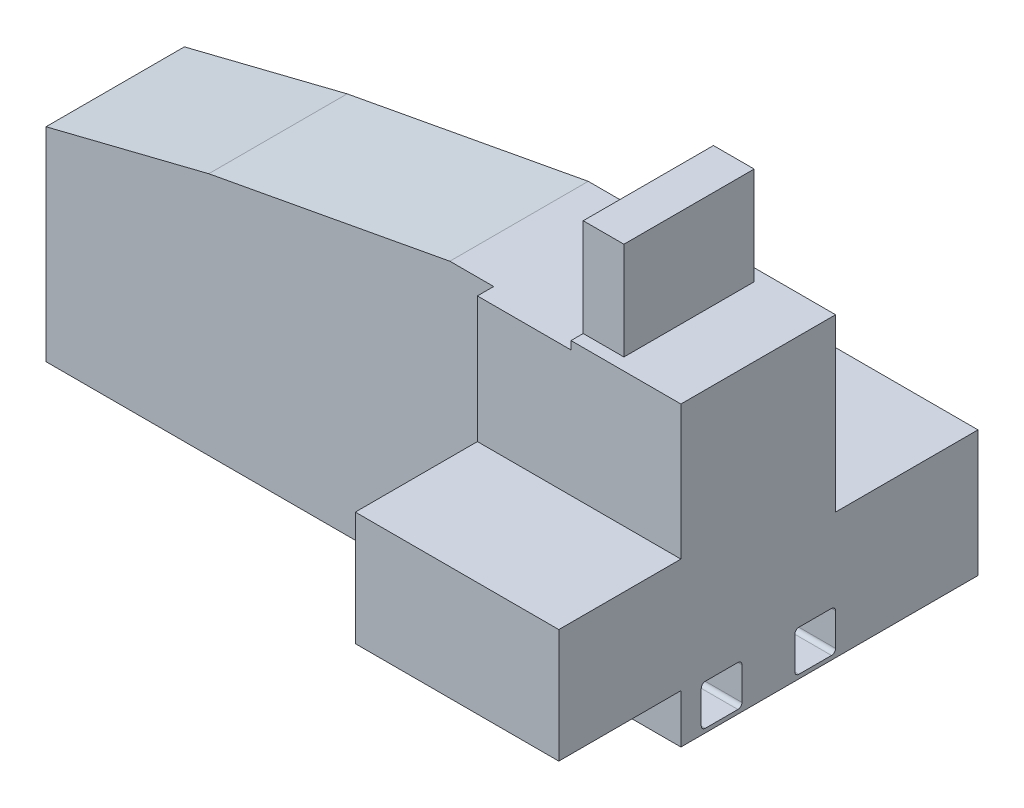
SolidWorks part; units mm, degrees
material "Custom Plastic"
ref_plane "Front Plane" through (0, 0, 0) normal (0, 0, 1) x (1, 0, 0)
ref_plane "Top Plane" through (0, 0, 0) normal (0, 1, 0) x (1, 0, 0)
ref_plane "Right Plane" through (0, 0, 0) normal (1, 0, 0) x (0, 0, -1)
sketch "Sketch1" plane through (0, 0, 0) normal (0, 0, 1) x (1, 0, 0)
  line L0 (-800, 0) -> (800, 0)
  line L1 (-800, 0) -> (-800, 500)
  line L2 (-400, 0) -> (-400, 600)
  line L3 (530, 0) -> (530, 970)
  line L4 (300, 0) -> (300, 730)
  line L5 (-800, 500) -> (-400, 600)
  line L6 (-400, 600) -> (300, 730)
  line L7 (300, 730) -> (530, 970)
  line L8 (800, 0) -> (530, 970)
  line L9 (-800, 500) -> (-800, 970)
  line L10 (-800, 970) -> (530, 970)
  dimension "D1" = 1600
  dimension "D2" = 500
  dimension "D3" = 400
  dimension "D4" = 800
  dimension "D5" = 600
  dimension "D6" = 270
  dimension "D7" = 500
  dimension "D8" = 970
  dimension "D9" = 730
sketch "Sketch2" plane through (0, 0, 0) normal (0, 1, 0) x (1, 0, 0)
  line L0 (800, -515) -> (800, 515)
  line L2 (800, -515) -> (300, -515)
  line L3 (300, -515) -> (300, -175)
  line L4 (300, -175) -> (-800, -175)
  line L5 (-800, -175) -> (-800, 175)
  line L6 (-800, 175) -> (-404, 175)
  line L7 (-404, 175) -> (-404, 355)
  line L8 (-404, 355) -> (-525, 355)
  line L9 (-525, 355) -> (-525, 175)
  line L10 (-525, 175) -> (300, 175)
  line L11 (300, 175) -> (300, 515)
  line L12 (300, 515) -> (800, 515)
  dimension "D1" = 800
  dimension "D2" = 500
  dimension "D3" = 175
  dimension "D4" = 175
  dimension "D5" = 530
  dimension "D6" = 121
  dimension "D7" = 500
  dimension "D8" = 350
  dimension "D9" = 1600
  dimension "D10" = 1030
  dimension "D11" = 515
  dimension "D12" = 275
extrude "Boss-Extrude1" add sketch "Sketch2" along normal blind 970 contours L12 L11 L10 L6 L5 L4 L3 L2 L0 | L8 L9 L6 L7 region at (207.7778, 0, 0) region at (-464.5, 0, -265)
extrude "Cut-Extrude1" cut sketch "Sketch1" against normal through all both and the other way through all contours L10 L9 L5 L6 L7 region at (-263.3113, 797.1661, 0)
sketch "Sketch3" plane through (-800, 0, 0) normal (-1, 0, 0) x (0, 0, 1)
  line L0 (-165, 0) -> (-65, 0)
  line L1 (175, 0) -> (-175, 0) construction
  line L2 (-55, 10) -> (-55, 120)
  line L3 (-55, 120) -> (-175, 120)
  line L4 (-175, 730) -> (-175, 0) construction
  line L5 (-175, 120) -> (-175, 10)
  line L11 (-165, 100) -> (-165, 20)
  line L12 (-155, 10) -> (-75, 10)
  line L13 (-65, 20) -> (-65, 100)
  line L14 (-75, 110) -> (-155, 110)
  line L19 (0, 137.8655) -> (0, -90.7951) construction
  line L20 (75, 110) -> (155, 110)
  line L21 (65, 20) -> (65, 100)
  line L22 (155, 10) -> (75, 10)
  line L23 (165, 100) -> (165, 20)
  line L24 (175, 120) -> (175, 10)
  line L25 (55, 120) -> (175, 120)
  line L26 (55, 10) -> (55, 120)
  line L27 (165, 0) -> (65, 0)
  arc A0 (175, 10) -> (165, 0) centre (165, 10) cw
  arc A1 (155, 10) -> (165, 20) centre (155, 20) ccw
  arc A2 (65, 20) -> (75, 10) centre (75, 20) ccw
  arc A3 (55, 10) -> (65, 0) centre (65, 10) ccw
  arc A4 (-65, 0) -> (-55, 10) centre (-65, 10) ccw
  arc A5 (-165, 0) -> (-175, 10) centre (-165, 10) cw
  arc A6 (-165, 20) -> (-155, 10) centre (-155, 20) ccw
  arc A7 (-75, 10) -> (-65, 20) centre (-75, 20) ccw
  arc A8 (-65, 100) -> (-75, 110) centre (-75, 100) ccw
  arc A9 (-165, 100) -> (-155, 110) centre (-155, 100) cw
  arc A10 (155, 110) -> (165, 100) centre (155, 100) cw
  arc A11 (75, 110) -> (65, 100) centre (75, 100) ccw
  point P27 (175, 0)
  point P30 (165, 10)
  point P33 (65, 10)
  point P36 (55, 0)
  point P39 (-55, 0)
  point P42 (-175, 0)
  point P45 (-165, 10)
  point P48 (-65, 10)
  point P51 (-65, 110)
  point P54 (-165, 110)
  point P57 (165, 110)
  point P60 (65, 110)
  dimension "D3" = 10
  dimension "D4" = 10
  dimension "D1" = 120
  dimension "D2" = 120
  dimension "D5" = 100
  dimension "D6" = 100
  dimension "D8" = 10
  dimension "D9" = 10
extrude "Cut-Extrude5" cut sketch "Sketch3" against normal blind 1625 contours A9 L11 A6 L12 A7 L13 A8 L14 | L21 A2 L22 A1 L23 L20 region at (-800, 60, -115) region at (-800, 60, 115)
sketch "Sketch4" plane through (0, 0, 0) normal (0, -1, 0) x (1, 0, 0)
  line L0 (-1069.2255, 0) -> (880.5229, 0) construction
  line L1 (0, 391.8823) -> (0, -321.383) construction
  line L2 (300, 175) -> (-800, 175) construction
  line L3 (-800, -175) -> (-525, -175) construction
  circle A0 centre (-498.5, 115) radius 8.5
  circle A1 centre (-501, -115) radius 8.5
  circle A2 centre (501, -115) radius 8.5
  circle A3 centre (498.5, 115) radius 8.5
  dimension "D1" = 17
  dimension "D4" = 17
  dimension "D2" = 498.5
  dimension "D3" = 60
  dimension "D5" = 501
  dimension "D6" = 60
extrude "Cut-Extrude6" cut sketch "Sketch4" against normal blind 78
sketch "Sketch5" plane through (0, 0, 515) normal (0, 0, 1) x (1, 0, 0)
  line L1 (800, 970) -> (800, 0) construction
  line L3 (800, 970) -> (530, 970) construction
  line L4 (630, 970) -> (530, 970)
  line L5 (530, 970) -> (530, 710)
  line L6 (530, 710) -> (155, 710)
  line L7 (800, 0) -> (300, 0) construction
  line L9 (155, 650) -> (155, 710)
  line L10 (800, 730) -> (630, 730)
  line L11 (800, 730) -> (800, 650)
  line L12 (630, 970) -> (630, 730)
  line L13 (155, 650) -> (800, 650)
  line L14 (155, 710) -> (155, 970)
  line L15 (155, 970) -> (800, 970)
  line L16 (800, 970) -> (800, 730)
  line M1 (530, 970) -> (300, 730)
  line M2 (300, 730) -> (300, 0)
  line M4 (800, 0) -> (800, 970)
  line M5 (800, 970) -> (530, 970)
  dimension "D1" = 170
  dimension "D2" = 100
  dimension "D3" = 375
  dimension "D4" = 710
  dimension "D5" = 650
  dimension "D6" = 730
extrude "Cut-Extrude8" cut sketch "Sketch5" against normal blind 1478 contours L15 L14 L6 M2 M1 | L6 L5 M1 M2 | L12 L10 M5 M4 region at (715, 850, 515) region at (290.5475, 861.1332, 515) region at (447.8571, 797.1429, 515)
sketch "Sketch6" plane through (0, 970, 0) normal (0, 1, 0) x (1, 0, 0)
  line L0 (530, 135) -> (530, -185)
  line L1 (530, 515) -> (530, -515) construction
  line L2 (530, 515) -> (530, -515) construction
  line L3 (530, -185) -> (630, -185)
  line L4 (630, 515) -> (630, -515) construction
  line L5 (630, -185) -> (630, 135)
  line L6 (630, 515) -> (630, -515) construction
  line L7 (630, 135) -> (530, 135)
  line L8 (530, 515) -> (630, 515) construction
  dimension "D1" = 380
  dimension "D2" = 700
extrude "Cut-Extrude9" cut sketch "Sketch6" against normal blind 240 flip side to cut
sketch "Sketch7" plane through (800, 0, 0) normal (1, 0, 0) x (0, 0, -1)
  line L0 (-515, 0) -> (-515, 120)
  line L1 (-515, 730) -> (-515, 0) construction
  line L2 (-515, 120) -> (-215, 120)
  line L3 (-215, 120) -> (-215, 0)
  line L4 (-515, 0) -> (515, 0) construction
  line L5 (-215, 0) -> (-515, 0)
  line L6 (-215, 400) -> (-215, 730)
  line L7 (-515, 730) -> (-515, 400)
  line L8 (-515, 400) -> (-215, 400)
  line L9 (515, 730) -> (-515, 730) construction
  line L10 (-215, 730) -> (-515, 730)
  line L11 (165, 730) -> (165, 310)
  line L12 (165, 310) -> (515, 310)
  line L13 (515, 730) -> (515, 0) construction
  line L14 (515, 310) -> (515, 730)
  line L15 (515, 730) -> (165, 730)
  dimension "D1" = 120
  dimension "D2" = 300
  dimension "D3" = 300
  dimension "D4" = 400
  dimension "D5" = 420
  dimension "D6" = 350
extrude "Cut-Extrude10" cut sketch "Sketch7" against normal through all
